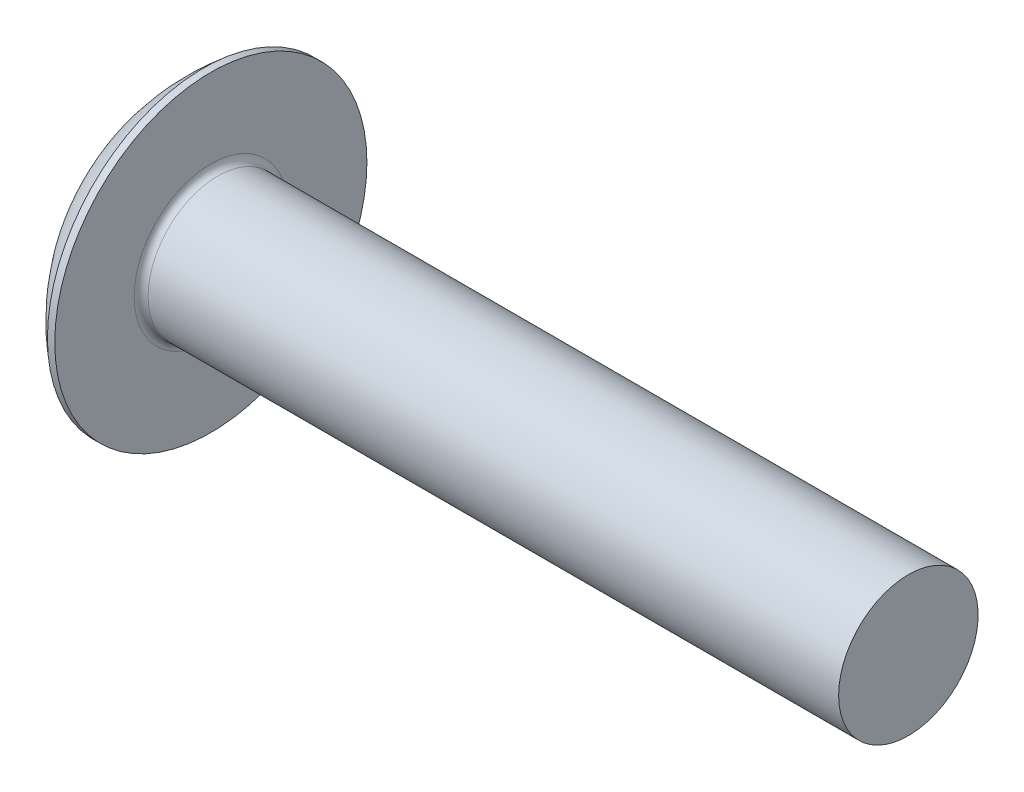
SolidWorks part; units mm, degrees
ref_plane "Front Plane" through (0, 0, 0) normal (0, 0, 1) x (1, 0, 0)
ref_plane "Top Plane" through (0, 0, 0) normal (0, 1, 0) x (1, 0, 0)
ref_plane "Right Plane" through (0, 0, 0) normal (1, 0, 0) x (0, 0, -1)
sketch "BodySke" plane through (0, 0, 0) normal (0, 0, 1) x (1, 0, 0)
  line L0 (0, 0) -> (120.5141, 0) construction
  line L1 (0, 0) -> (0, 50.5629) construction
  line L2 (4.7, 8.95) -> (4.7, 4)
  line L3 (4.7, 4) -> (44.7, 4)
  line L4 (44.7, 4) -> (44.7, 0)
  line L5 (0, 0) -> (44.7, 0)
  line L6 (4.7, 8.95) -> (4.2787, 8.95)
  line L7 (5.95, 10.4217) -> (5.95, -3.1786) construction
  line L8 (7.2, 9.5609) -> (7.2, -6.7938) construction
  arc A0 (0, 0) -> (4.2787, 8.95) centre (11.5, 0) cw
  point P14 (44.7, 3.3095)
  dimension "Thread_minor" = 6.619
  dimension "Advance" = 1.25
revolve "BaseBody" add sketch "BodySke" angle 360 about L0
cosmetic thread "ThreadCosmetic" [suppressed] parameters "Thread_minor"=6.619
fillet "Fillet1" radius 0.4 1 edges at (4.7, 0, 4)
sketch "SlotSke" plane through (0, 0, 0) normal (1, 0, 0) x (0, 0, -1)
  line L1 (8.95, 1.155) -> (-8.95, 1.155)
  line L2 (8.95, 1.155) -> (8.95, -1.155)
  line L3 (8.95, -1.155) -> (-8.95, -1.155)
  line L4 (-8.95, 1.155) -> (-8.95, -1.155)
  dimension "D1" = 17.9
  dimension "D2" = 8.95
  dimension "D4" = 1.155
extrude "Slot" cut sketch "SlotSke" along normal blind 2.17
sketch "ThdSchSke" plane through (0, 0, 0) normal (0, 0, 1) x (1, 0, 0)
  line L0 (0, 0) -> (54.7976, 0) construction
  line L1 (44.3013, 4.7973) -> (44.3013, 4)
  line L2 (44.3013, 4.7973) -> (45.0987, 4.7973)
  line L3 (45.0987, 4.7973) -> (45.0987, 4)
  line L4 (45.0987, 4) -> (44.7, 3.3095)
  line L5 (44.7, 3.3095) -> (44.3013, 4)
  line L6 (4.7, 4) -> (44.7, 4) construction
revolve "ThreadSchematic" [suppressed] cut sketch "ThdSchSke" angle 360 about L0
pattern_linear "ThdSchPat" [suppressed] count 31 along (-1, 0, 0) of bodies 103
equation "\"Thread_minor@ThreadCosmetic\" = \"Thread_minor@BodySke\""
equation "\"D1@SlotSke\" = \"Head_dia@BodySke\""
equation "\"D2@SlotSke\" = \"D1@SlotSke\" / 2"
equation "\"D4@SlotSke\" = \"Slot_width@SlotSke\" / 2"
equation "\"Advance@ThdSchPat\" = \"Advance@BodySke\""
equation "\"D1@ThdSchPat\" =  int(  ( \"Length@BodySke\" - \"Thread_runout@BodySke\" )  / \"Advance@BodySke\" ) + 1 "
